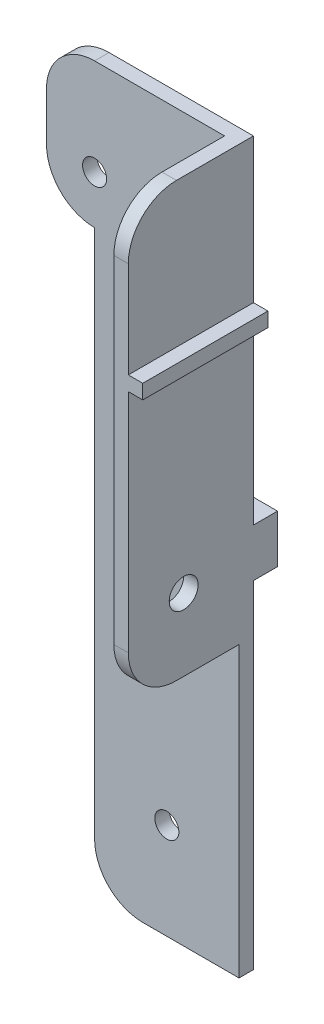
SolidWorks part; units mm, degrees
ref_plane "Front Plane" through (0, 0, 0) normal (0, 0, 1) x (1, 0, 0)
ref_plane "Top Plane" through (0, 0, 0) normal (0, 1, 0) x (1, 0, 0)
ref_plane "Right Plane" through (0, 0, 0) normal (1, 0, 0) x (0, 0, -1)
sketch "Sketch1" plane through (0, 0, 0) normal (0, 0, 1) x (1, 0, 0)
  line L0 (0, 150) -> (-10, 150)
  line L1 (0, 0) -> (30, 0)
  line L2 (0, 0) -> (0, 120)
  line L3 (0, 150) -> (30, 150)
  line L4 (30, 0) -> (30, 150)
  line L5 (30, 150) -> (-10, 150)
  line L6 (30, 150) -> (30, 120)
  line L7 (0, 120) -> (-10, 120)
  line L8 (-10, 150) -> (-10, 120)
  line L13 (30, 75) -> (30, 80)
  line L14 (30, 80) -> (0, 80)
  line L15 (0, 75) -> (0, 80)
  line L17 (0, 75) -> (0, 70)
  line L18 (0, 70) -> (30, 70)
  line L19 (30, 75) -> (30, 70)
  circle A0 centre (0, 130) radius 2.5
  circle A1 centre (15, 20) radius 2.5
  dimension "D9" = 5
  dimension "D10" = 5
  dimension "D1" = 150
  dimension "D2" = 30
  dimension "D3" = 30
  dimension "D4" = 40
  dimension "D8" = 20
extrude "Boss-Extrude1" add sketch "Sketch1" against normal blind 3 contours L14 L4 L3 L0 L8 L7 L2 A0 | L18 L2 L1 L4 A1 region at (12.6031, 117.3969, 0) region at (15, 35.1416, 0)
sketch "Sketch3" plane through (0, 0, 0) normal (0, 0, 1) x (1, 0, 0)
  line L1 (0, 80) -> (30, 80)
  line L2 (0, 80) -> (0, 70)
  line L3 (0, 70) -> (30, 70)
  line L4 (30, 80) -> (30, 70)
extrude "Boss-Extrude2" add sketch "Sketch3" against normal blind 8
sketch "Sketch4" plane through (0, 0, 0) normal (0, 0, 1) x (1, 0, 0)
  line L0 (0, 0) -> (30, 0) construction
  line L1 (30, 150) -> (27, 150)
  line L2 (30, 150) -> (30, 0)
  line L3 (30, 0) -> (27, 0)
  line L4 (27, 150) -> (27, 0)
  dimension "D1" = 3
extrude "Boss-Extrude4" add sketch "Sketch4" along normal blind 23 contours L2 L1 L4 L3
sketch "Sketch5" plane through (27, 0, 0) normal (-1, 0, 0) x (0, 0, 1)
  line L0 (11.5, 150) -> (11.5, 0) construction
  line L1 (23, 150) -> (0, 150) construction
  line L2 (23, 0) -> (0, 0) construction
  circle A0 centre (11.5, 75) radius 3
  dimension "D1" = 6
extrude "Cut-Extrude1" cut sketch "Sketch5" against normal blind 23
sketch "Sketch6" plane through (30, 0, 0) normal (1, 0, 0) x (0, 0, -1)
  line L0 (3, 80) -> (3, 150) construction
  line L1 (-23, 150) -> (3, 150)
  line L2 (-23, 150) -> (-23, 120)
  line L3 (-23, 120) -> (3, 120)
  line L4 (3, 150) -> (3, 120)
  line L6 (-23, 120) -> (3, 120)
  line L7 (-23, 120) -> (-23, 117)
  line L8 (-23, 117) -> (3, 117)
  line L9 (3, 120) -> (3, 117)
  line M8 (-23, 150) -> (-23, 0)
  line M14 (3, 80) -> (3, 150)
  dimension "D1" = 30
  dimension "D2" = 3
extrude "Boss-Extrude5" add sketch "Sketch6" along normal blind 3 contours L8 L3 M8 M14 region at (30, 118.5, 10)
fillet "Fillet1" radius 10 5 edges at (0, 0, -1.5) (28.5, 0, 23) (28.5, 150, 23) (-10, 120, -1.5) (-10, 150, -1.5)
sketch "Sketch7" plane through (30, 0, 0) normal (1, 0, 0) x (0, 0, -1)
  line L1 (0, 0) -> (-36.729, 0)
  line L2 (0, 0) -> (0, 60)
  line L3 (0, 60) -> (-36.729, 60)
  line L4 (-36.729, 0) -> (-36.729, 60)
  dimension "D1" = 60
extrude "Cut-Extrude2" cut sketch "Sketch7" against normal blind 3
fillet "Fillet2" radius 10 1 edges at (28.5, 60, 23)
sketch "Sketch8" plane through (30, 0, 0) normal (1, 0, 0) x (0, 0, -1)
  line L0 (3, 80) -> (8, 80)
  line L1 (0, 60) -> (0, 0)
  dimension "D1" = 5
  dimension "D2" = 60
